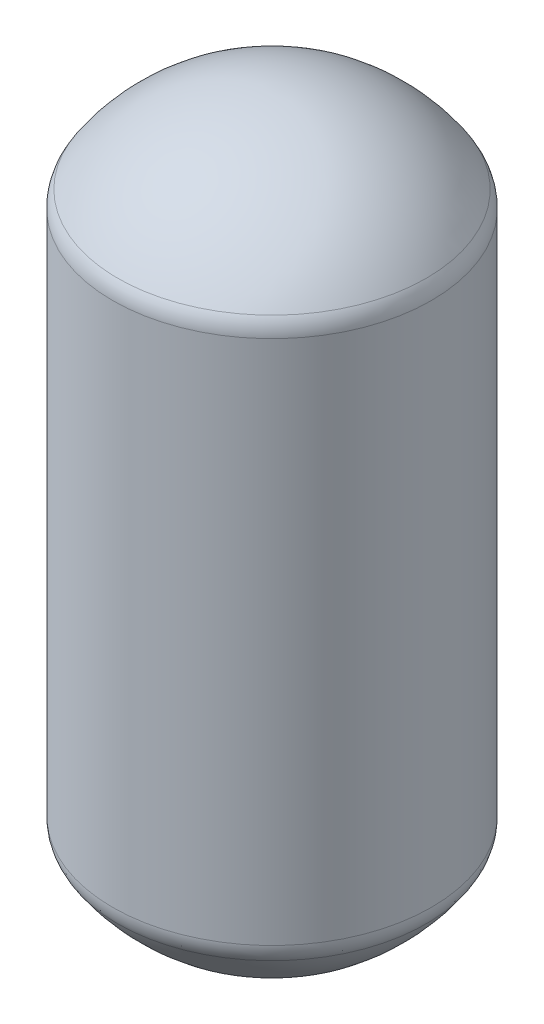
SolidWorks part; units mm, degrees
material "Custom Plastic"
ref_plane "Front Plane" through (0, 0, 0) normal (0, 0, 1) x (1, 0, 0)
ref_plane "Top Plane" through (0, 0, 0) normal (0, 1, 0) x (1, 0, 0)
ref_plane "Right Plane" through (0, 0, 0) normal (1, 0, 0) x (0, 0, -1)
sketch "Sketch1" plane through (0, 0, 0) normal (0, 0, 1) x (1, 0, 0)
  line L0 (0, 0) -> (0, 1200) construction
  line L1 (-133.985, 76.2) -> (133.985, 76.2) construction
  line L2 (-133.985, 0) -> (133.985, 0) construction
  line L3 (-133.985, 0) -> (-133.985, 1200) construction
  line L4 (-133.985, 1200) -> (133.985, 1200) construction
  line L5 (133.985, 0) -> (133.985, 1200) construction
  line L6 (-133.985, 0) -> (133.985, 1200) construction
  line L7 (-133.985, 1200) -> (133.985, 0) construction
  line L8 (-133.985, 685.1) -> (133.985, 685.1) construction
  line L9 (-133.985, 1123.8) -> (133.985, 1123.8) construction
  line L10 (-133.985, 608.9) -> (133.985, 608.9) construction
  line L11 (-133.985, 532.7) -> (133.985, 532.7) construction
  line L12 (-133.985, 608.9) -> (0, 608.9) construction
  line L13 (0, 608.9) -> (133.985, 608.9) construction
  line L14 (-133.985, 1123.8) -> (-133.985, 685.1)
  line L15 (133.985, 1123.8) -> (133.985, 685.1) construction
  line L16 (-133.985, 532.7) -> (-133.985, 76.2)
  line L17 (133.985, 532.7) -> (133.985, 76.2) construction
  line L18 (-130.81, 531.8223) -> (-130.81, 77.0777)
  line L19 (130.81, 531.8223) -> (130.81, 77.0777) construction
  line L20 (-130.81, 1122.9223) -> (-130.81, 685.9777)
  line L21 (130.81, 1122.9223) -> (130.81, 685.9777) construction
  line L22 (0, 612.075) -> (0, 608.9)
  line L23 (0, 605.725) -> (0, 608.9)
  line L24 (0, 3.175) -> (0, 0)
  line L25 (0, 1200) -> (0, 1196.825)
  arc A0 (0, 0) -> (-133.985, 76.2) centre (0, 155.8951) cw
  arc A1 (0, 0) -> (133.985, 76.2) centre (0, 155.8951) ccw construction
  arc A2 (0, 1200) -> (133.985, 1123.8) centre (0, 1044.1049) cw construction
  arc A3 (0, 1200) -> (-133.985, 1123.8) centre (0, 1044.1049) ccw
  arc A4 (0, 608.9) -> (-133.985, 532.7) centre (0, 453.0049) ccw
  arc A5 (0, 608.9) -> (133.985, 532.7) centre (0, 453.0049) cw construction
  arc A6 (0, 608.9) -> (-133.985, 685.1) centre (0, 764.7951) cw
  arc A7 (0, 608.9) -> (133.985, 685.1) centre (0, 764.7951) ccw construction
  arc A8 (0, 605.725) -> (-130.81, 531.8223) centre (0, 453.0049) ccw
  arc A9 (0, 3.175) -> (-130.81, 77.0777) centre (0, 155.8951) cw
  arc A10 (0, 3.175) -> (130.81, 77.0777) centre (0, 155.8951) ccw construction
  arc A11 (0, 605.725) -> (130.81, 531.8223) centre (0, 453.0049) cw construction
  arc A12 (0, 612.075) -> (-130.81, 685.9777) centre (0, 764.7951) cw
  arc A13 (0, 1196.825) -> (-130.81, 1122.9223) centre (0, 1044.1049) ccw
  arc A14 (0, 1196.825) -> (130.81, 1122.9223) centre (0, 1044.1049) cw construction
  arc A15 (0, 612.075) -> (130.81, 685.9777) centre (0, 764.7951) ccw construction
  point P3 (0, 600)
  dimension "D3" = 76.2
  dimension "D1" = 1200
  dimension "D2" = 267.97
  dimension "D4" = 76.2
  dimension "D5" = 76.2
  dimension "D6" = 1200
  dimension "D7" = 591.1
  dimension "D8" = 76.2
  dimension "D9" = 3.175
  dimension "D10" = 3.175
revolve "Revolve1" add sketch "Sketch1" angle 360 about L0 region at (-6.2347, 607.3125, 0)
fillet "Fillet1" radius 25.4 4 edges at (0, 77.0777, -130.81) (0, 76.2, -133.985) (0, 531.8223, -130.81) (0, 532.7, -133.985)
